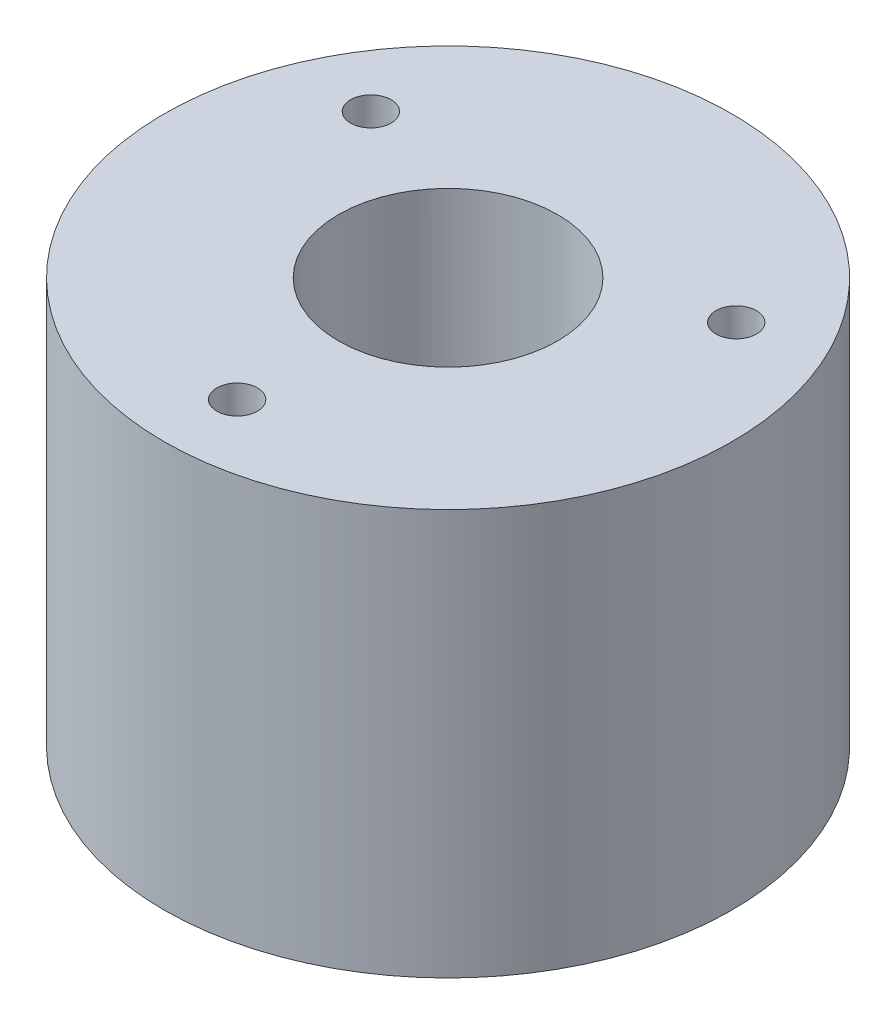
SolidWorks part; units mm, degrees
material "6061-T6 (SS)"
ref_plane "Front Plane" through (0, 0, 0) normal (0, 0, 1) x (1, 0, 0)
ref_plane "Top Plane" through (0, 0, 0) normal (0, 1, 0) x (1, 0, 0)
ref_plane "Right Plane" through (0, 0, 0) normal (1, 0, 0) x (0, 0, -1)
sketch "Sketch1" plane through (0, 0, 0) normal (0, 1, 0) x (1, 0, 0)
  circle A0 centre (0, 0) radius 22.225
  circle A1 centre (0, 0) radius 8.5725
  dimension "D1" = 44.45
  dimension "D2" = 17.145
extrude "Boss-Extrude1" add sketch "Sketch1" along normal blind 31.75
sketch "Sketch2" plane through (0, 0, 0) normal (0, -1, 0) x (1, 0, 0)
  line L1 (6.9215, 11.9884) -> (-6.9215, 11.9884)
  line L2 (-6.9215, 11.9884) -> (-13.843, 0)
  line L3 (-13.843, 0) -> (-6.9215, -11.9884)
  line L4 (-6.9215, -11.9884) -> (6.9215, -11.9884)
  line L5 (6.9215, -11.9884) -> (13.843, 0)
  line L6 (13.843, 0) -> (6.9215, 11.9884)
  circle A0 centre (0, 0) radius 11.9884 construction
  circle A1 centre (-6.9215, 11.9884) radius 1.5875
  circle A2 centre (6.9215, 11.9884) radius 1.5875
  circle A3 centre (13.843, 0) radius 1.5875
  circle A4 centre (6.9215, -11.9884) radius 1.5875
  circle A5 centre (-6.9215, -11.9884) radius 1.5875
  circle A6 centre (-13.843, 0) radius 1.5875
  point P22 (0, 0)
  circle M3 centre (0, 0) radius 8.5725
  dimension "D2" = 3.175
  dimension "D3" = 6
  dimension "D1" = 13.843
extrude "Cut-Extrude1" cut sketch "Sketch2" against normal blind 9.9219 contours L2 A6 L3 | L3 A6 L2 | A6 L3 A5 L4 A4 L5 A3 L6 A2 L1 A1 L2 M3 | L3 A5 L4 | L4 A5 L3 | L4 A4 L5 | L5 A4 L4 | L5 A3 L6 | L6 A3 L5 | L6 A2 L1 | L1 A2 L6 | L1 A1 L2 | L2 A1 L1 region at (-6.4839, 0, 11.2304) region at (-7.1403, 0, 12.3674) region at (0, 0, 11.634) region at (7.1403, 0, 12.3674) region at (6.4839, 0, 11.2304) region at (-12.9678, 0, 0) region at (-14.2806, 0, 0) region at (14.2806, 0, 0) region at (12.9678, 0, 0) region at (-6.4839, 0, -11.2304) region at (-7.1403, 0, -12.3674) region at (7.1403, 0, -12.3674) region at (6.4839, 0, -11.2304)
fillet "Fillet1" radius 3.175 12 edges at (-13.0493, 4.9609, -1.3748) (-7.7153, 4.9609, -10.6136) (-5.334, 4.9609, -11.9884) (5.334, 4.9609, -11.9884) (7.7152, 4.9609, -10.6136) (13.0492, 4.9609, -1.3748) (13.0493, 4.9609, 1.3748) (7.7153, 4.9609, 10.6136) (5.334, 4.9609, 11.9884) (-5.334, 4.9609, 11.9884) (-7.7153, 4.9609, 10.6136) (-13.0492, 4.9609, 1.3748)
sketch "Sketch3" plane through (0, 0, 0) normal (0, -1, 0) x (1, 0, 0)
  line L0 (3.3717, 11.9884) -> (-3.3717, 11.9884) construction
  circle A0 centre (0, 16.51) radius 1.5875
  circle A1 centre (14.2981, -8.255) radius 1.5875
  circle A2 centre (-14.2981, -8.255) radius 1.5875
  point P2 (0, 11.9884)
  point P12 (0, 0)
  dimension "D2" = 3.175
  dimension "D1" = 16.51
  dimension "D3" = 3
extrude "Cut-Extrude2" cut sketch "Sketch3" against normal through all
